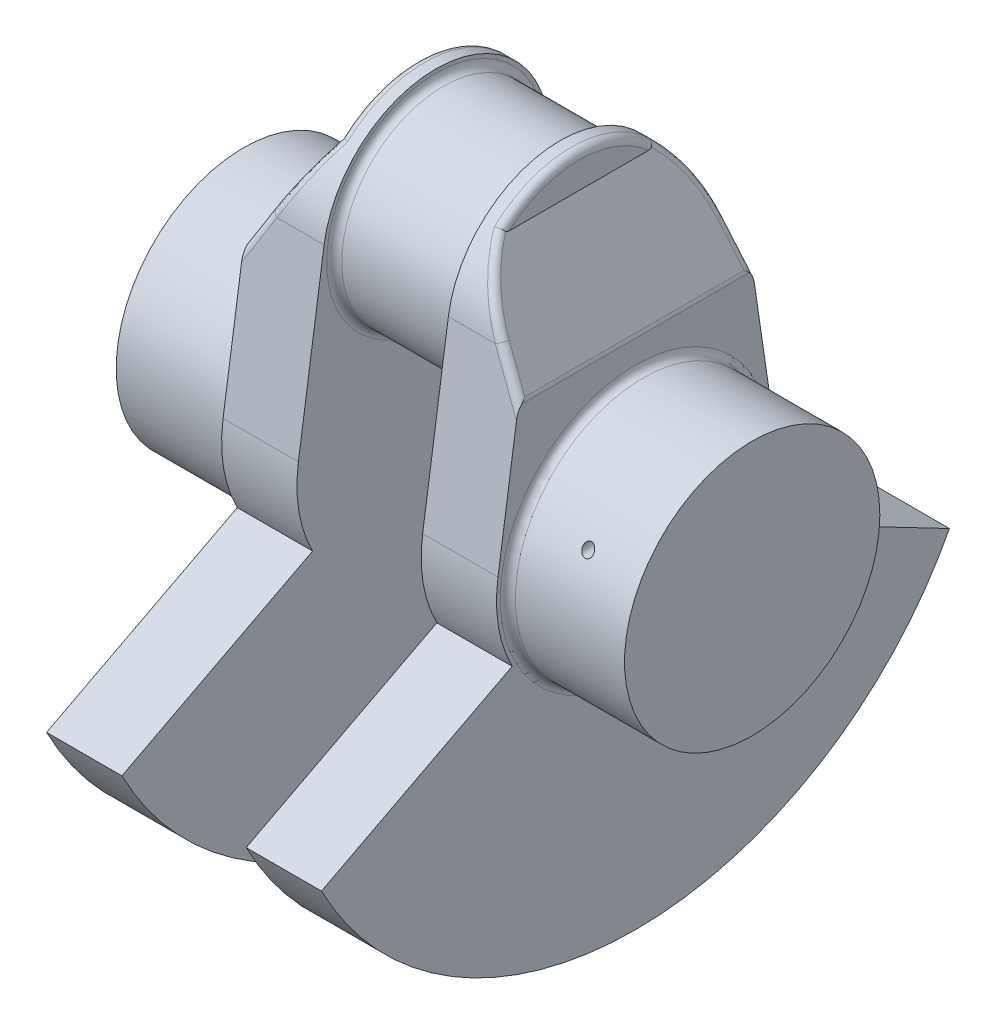
SolidWorks part; units mm, degrees
ref_plane "Спереди" through (0, 0, 0) normal (0, 0, 1) x (1, 0, 0)
ref_plane "Сверху" through (0, 0, 0) normal (0, 1, 0) x (1, 0, 0)
ref_plane "Справа" through (0, 0, 0) normal (1, 0, 0) x (0, 0, -1)
sketch "Эскиз3" plane through (0, 0, 0) normal (1, 0, 0) x (0, 0, -1)
  circle A0 centre (0, 0) radius 33.9
  dimension "D1" = 67.8
extrude "Бобышка-Вытянуть1" add sketch "Эскиз3" along normal blind 31 contours A0
sketch "Эскиз4" plane through (31, 0, 0) normal (1, 0, 0) x (0, 0, -1)
  line L0 (-29.6818, 51.8579) -> (-36.5086, 5.3602)
  line L1 (29.6818, 51.8579) -> (36.5086, 5.3602)
  line L2 (-83.379, -43.4044) -> (0, 0)
  line L3 (0, -47) -> (0, 0)
  line L4 (83.379, -43.4044) -> (0, 0)
  circle A0 centre (0, 0) radius 36.9
  circle A1 centre (0, 47.5) radius 30
  circle A2 centre (0, 0) radius 33.9 construction
  arc A3 (83.379, -43.4044) -> (-83.379, -43.4044) centre (0, 0) cw
  circle M1 centre (0, 0) radius 33.9
  dimension "D1" = 47.5
  dimension "D2" = 60
  dimension "D4" = 94
  dimension "D3" = 3
  dimension "D5" = 117.5
extrude "Бобышка-Вытянуть2" add sketch "Эскиз4" along normal blind 20 contours A1 A0 | A0 A1 M1 | A1 M1 | A1 A0 L1 | A1 A0 M1 | A1 M1 | A1 L0 A0 | A0 | L4 A3 L2 region at (31, 28.8579, 30.213) region at (31, 53.1931, 0) region at (31, 28.8579, -30.213) region at (31, 36.4222, 0) region at (31, 2.6521, -36.3209) region at (31, 25.8071, 0) region at (31, 5.6798, 0)
sketch "Эскиз6" plane through (0, 0, 0) normal (0, 0, 1) x (1, 0, 0)
  line L0 (31, 77.5) -> (46, 77.5)
  line L1 (51, 77.5) -> (31, 77.5) construction
  line L2 (46, 77.5) -> (46, 68.5)
  line L3 (46, 68.5) -> (31, 42.5192)
  line L4 (31, 77.5) -> (31, 51.8579) construction
  line L5 (31, 42.5192) -> (31, 77.5)
  dimension "D1" = 5
  dimension "D2" = 60
  dimension "D3" = 9
extrude "Вырез-Вытянуть1" cut sketch "Эскиз6" against normal through all and the other way through all
fillet "Скругление1" radius 2 6 edges at (31, 42.5192, 0) (33.6958, 47.1886, -30.3673) (41.5742, 60.8343, -26.8737) (33.6958, 47.1886, 30.3673) (41.5742, 60.8343, 26.8737) (46, 77.5, 0)
sketch "Эскиз5" plane through (51, 0, 0) normal (1, 0, 0) x (0, 0, -1)
  circle A1 centre (0, 47.5) radius 27
  dimension "D1" = 54
  dimension "D2" = 47.5
extrude "Бобышка-Вытянуть3" add sketch "Эскиз5" along normal blind 16.5
fillet "Скругление2" radius 2 1 edges at (51, 47.5, -27)
fillet "Скругление3" radius 2 1 edges at (31, 0, -33.9)
ref_axis "Ось1" through (67.5, -102.575, 0) along (0, 1, 0)
mirror "Зеркальное отражение4" about plane through (67.5, 47.5, 0) normal (1, 0, 0) of bodies 103 111
sketch "Эскиз10" plane through (0, 0, 0) normal (0, 0, 1) x (1, 0, 0)
  line L0 (67.5, 74.5) -> (67.5, 20.5)
  line L1 (82, 74.5) -> (53, 74.5) construction
  line L2 (53, 20.5) -> (82, 20.5) construction
  circle A0 centre (67.5, 47.5) radius 1.5
  point P8 (0, 0)
ref_axis "Ось13" through (67.5, 47.5, 0) along (0, 0, 1)
ref_plane "Плоскость10" through (37.4431, 64.8534, 0) normal (-0.5, -0.866, 0) x (0, 0, 1)
ref_axis "Ось9" through (42.2817, 62.0598, 84.6452) along (0, 0, -1)
sketch "Эскиз12" plane through (4.8386, -2.7936, 0) normal (-0.866, 0.5, 0) x (0, 0, 1)
  line L0 (-29.1101, 52.8586) -> (29.1101, 52.8586)
  line L1 (29.1101, 52.8586) -> (27.703, 63.9253) construction
  line L2 (-29.1101, 52.8586) -> (29.1101, 52.8586) construction
  line L3 (-22.2611, 74.8862) -> (22.2611, 74.8862) construction
  circle A0 centre (0, 74.8862) radius 1.5
extrude "Вырез-Вытянуть5" cut sketch "Эскиз12" against normal offset from surface (95 mm away) 95 contours A0 region at (42.2817, 62.0598, 0) up to face at (40.1452, 58.3592, 0.0296)
ref_axis "Ось10" through (182.3675, -18.8188, 0) along (-0.866, 0.5, 0)
ref_plane "Плоскость11" through (121, 0, 0) normal (1, 0, 0) x (0, 0, -1)
ref_axis "Ось12" through (121, 16.6118, -34.5271) along (0, 0, 1)
ref_plane "Плоскость13" through (0, 0, 0) normal (0, 0, 1) x (1, 0, 0)
sketch "Эскиз14" plane through (0, 0, 0) normal (0, 0, 1) x (1, 0, 0)
  line L0 (121, -91.7169) -> (121, 91.7169) construction
  line L1 (18.1644, 75.9839) -> (56.7218, 53.7228) construction
  circle A0 centre (121, 16.6118) radius 1.5
extrude "Вырез-Вытянуть6" cut sketch "Эскиз14" against normal through all both and the other way through all
